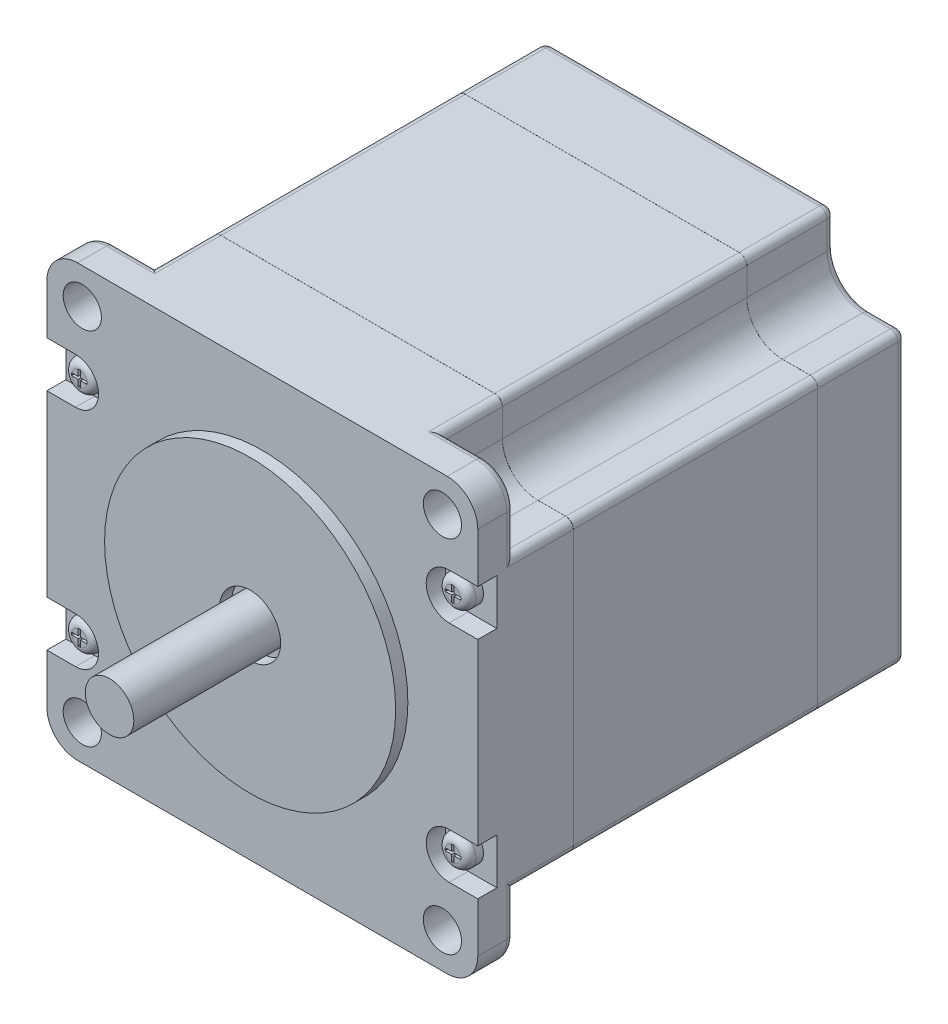
SolidWorks part; units mm, degrees
material "1060 Alloy"
ref_plane "Front Plane" through (0, 0, 0) normal (0, 0, 1) x (1, 0, 0)
ref_plane "Top Plane" through (0, 0, 0) normal (0, 1, 0) x (1, 0, 0)
ref_plane "Right Plane" through (0, 0, 0) normal (1, 0, 0) x (0, 0, -1)
sketch "Sketch1" plane through (0, 0, 0) normal (0, 0, 1) x (1, 0, 0)
  line L1 (-28.2, -28.2) -> (28.2, -28.2)
  line L2 (-28.2, -28.2) -> (-28.2, 28.2)
  line L3 (-28.2, 28.2) -> (28.2, 28.2)
  line L4 (28.2, -28.2) -> (28.2, 28.2)
  line L5 (-28.2, -28.2) -> (28.2, 28.2) construction
  line L6 (-28.2, 28.2) -> (28.2, -28.2) construction
  point P0 (0, 0)
  dimension "D1" = 56.4
  dimension "D2" = 56.4
extrude "Boss-Extrude1" add sketch "Sketch1" against normal blind 56
sketch "Sketch2" plane through (0, 0, 0) normal (0, 0, 1) x (1, 0, 0)
  circle A0 centre (0, 0) radius 19.05
  dimension "D1" = 38.1
extrude "Boss-Extrude2" add sketch "Sketch2" along normal blind 1.6
sketch "Sketch3" plane through (0, 0, 0) normal (0, 0, 1) x (1, 0, 0)
  line L0 (-23.57, 23.57) -> (23.57, 23.57) construction
  line L1 (23.57, 23.57) -> (23.57, -23.57) construction
  line L2 (23.57, -23.57) -> (-23.57, -23.57) construction
  line L3 (-23.57, -23.57) -> (-23.57, 23.57) construction
  line L4 (23.57, 23.57) -> (-23.57, -23.57) construction
  circle A0 centre (-23.57, 23.57) radius 2.5
  circle A1 centre (23.57, 23.57) radius 2.5
  circle A2 centre (23.57, -23.57) radius 2.5
  circle A3 centre (-23.57, -23.57) radius 2.5
  dimension "D1" = 5
  dimension "D2" = 47.14
  dimension "D3" = 47.14
extrude "Cut-Extrude1" cut sketch "Sketch3" against normal blind 10
sketch "Sketch6" plane through (0, 0, -56) normal (0, 0, -1) x (-1, 0, 0)
  line L0 (-18.92, 23.57) -> (-18.92, 28.2)
  line L1 (-28.2, 28.2) -> (28.2, 28.2) construction
  line L2 (-23.57, 18.92) -> (-28.2, 18.92)
  line L3 (-28.2, -28.2) -> (-28.2, 28.2) construction
  line L4 (-28.2, 0) -> (28.2, 0) construction
  line L5 (28.2, 28.2) -> (28.2, -28.2) construction
  line L6 (0, 28.2) -> (0, -28.2) construction
  line L7 (28.2, -28.2) -> (-28.2, -28.2) construction
  line L8 (-18.92, 28.2) -> (-28.2, 28.2)
  line L9 (-28.2, 28.2) -> (-28.2, 18.92)
  line L10 (28.2, 28.2) -> (28.2, 18.92)
  line L11 (18.92, 28.2) -> (28.2, 28.2)
  line L12 (23.57, 18.92) -> (28.2, 18.92)
  line L13 (18.92, 23.57) -> (18.92, 28.2)
  line L14 (-28.2, -28.2) -> (-28.2, -18.92)
  line L15 (-18.92, -28.2) -> (-28.2, -28.2)
  line L16 (-23.57, -18.92) -> (-28.2, -18.92)
  line L17 (-18.92, -23.57) -> (-18.92, -28.2)
  line L18 (18.92, -23.57) -> (18.92, -28.2)
  line L19 (23.57, -18.92) -> (28.2, -18.92)
  line L20 (18.92, -28.2) -> (28.2, -28.2)
  line L21 (28.2, -28.2) -> (28.2, -18.92)
  circle A0 centre (-23.57, 23.57) radius 2.5 construction
  arc A4 (23.57, 18.92) -> (18.92, 23.57) centre (23.57, 23.57) cw
  arc A5 (-23.57, -18.92) -> (-18.92, -23.57) centre (-23.57, -23.57) cw
  arc A6 (-23.57, 18.92) -> (-18.92, 23.57) centre (-23.57, 23.57) ccw
  arc A7 (23.57, -18.92) -> (18.92, -23.57) centre (23.57, -23.57) ccw
  dimension "D1" = 4.65
extrude "Cut-Extrude2" cut sketch "Sketch6" against normal offset from surface (51.2 mm away) 4.8 up to face at (-21.07, -23.57, 0)
fillet "Fillet1" radius 4 4 edges at (28.2, -28.2, -2.4) (-28.2, -28.2, -2.4) (-28.2, 28.2, -2.4) (28.2, 28.2, -2.4)
sketch "Sketch7" plane through (-28.2, 0, 0) normal (-1, 0, 0) x (0, 0, 1)
  line L0 (-4.8, 28.2) -> (-56, 28.2) construction
  line L1 (-12.51, -28.2) -> (-44.49, -28.2)
  line L2 (-12.51, -28.2) -> (-12.51, 28.2)
  line L3 (-12.51, 28.2) -> (-44.49, 28.2)
  line L4 (-44.49, -28.2) -> (-44.49, 28.2)
  line L5 (-12.51, -28.2) -> (-44.49, 28.2) construction
  line L6 (-12.51, 28.2) -> (-44.49, -28.2) construction
  line L7 (-28.5, -28.2) -> (-28.5, 28.2) construction
  line L9 (-56, 0) -> (0, 0) construction
  line L10 (-56, 18.92) -> (-56, -18.92) construction
  line L11 (-44.5, -28.21) -> (-44.5, 28.21)
  line L12 (-12.5, 28.21) -> (-44.5, 28.21)
  line L13 (-12.5, -28.21) -> (-12.5, 28.21)
  line L14 (-12.5, -28.21) -> (-44.5, -28.21)
  point P0 (-28.5, 0)
  dimension "D1" = 32
  dimension "D3" = 11.5
  dimension "D2" = 0.01
extrude "Cut-Extrude3" cut sketch "Sketch7" against normal through all
sketch "Sketch8" plane through (0, 0, -56) normal (0, 0, -1) x (-1, 0, 0)
  circle A0 centre (0, 0) radius 6
  dimension "D1" = 12
extrude "Cut-Extrude4" cut sketch "Sketch8" against normal blind 3
sketch "Sketch9" plane through (0, 0, -53) normal (0, 0, -1) x (-1, 0, 0)
  circle A0 centre (0, 0) radius 3.175
  dimension "D1" = 6.35
extrude "Boss-Extrude3" add sketch "Sketch9" along normal blind 1.5 separate body
chamfer "Chamfer1" distance 0.5 angle 45 1 edges at (-3.175, 0, -54.5)
sketch "Sketch10" plane through (0, 0, 1.6) normal (0, 0, 1) x (1, 0, 0)
  circle A0 centre (0, 0) radius 4
  dimension "D1" = 8
extrude "Cut-Extrude5" cut sketch "Sketch10" against normal up to surface (1.6 mm away) up to face at (-21.07, -23.57, 0)
sketch "Sketch11" plane through (0, 0, 0) normal (0, 0, 1) x (1, 0, 0)
  circle A0 centre (0, 0) radius 3.175
  dimension "D1" = 6.35
extrude "Boss-Extrude4" add sketch "Sketch11" along normal blind 20 separate body
sketch "Sketch13" plane through (0, 0, 0) normal (0, 0, 1) x (1, 0, 0)
  line L0 (-28.2, 24.2) -> (-28.2, -24.2) construction
  line L1 (24.2, 28.2) -> (-24.2, 28.2) construction
  line L2 (-24.45, 17.7) -> (-28.2, 17.7)
  line L3 (-28.2, 17.7) -> (-28.2, 11.7)
  line L4 (-28.2, 11.7) -> (-24.45, 11.7)
  line L5 (0, 28.2) -> (0, 0) construction
  line L6 (-28.2, 0) -> (0, 0) construction
  line L7 (28.2, 11.7) -> (24.45, 11.7)
  line L8 (28.2, 17.7) -> (28.2, 11.7)
  line L9 (24.45, 17.7) -> (28.2, 17.7)
  line L10 (24.45, -17.7) -> (28.2, -17.7)
  line L11 (28.2, -17.7) -> (28.2, -11.7)
  line L12 (28.2, -11.7) -> (24.45, -11.7)
  line L13 (-28.2, -11.7) -> (-24.45, -11.7)
  line L14 (-28.2, -17.7) -> (-28.2, -11.7)
  line L15 (-24.45, -17.7) -> (-28.2, -17.7)
  arc A0 (-24.45, 11.7) -> (-24.45, 17.7) centre (-24.45, 14.7) ccw
  arc A1 (24.45, 11.7) -> (24.45, 17.7) centre (24.45, 14.7) cw
  arc A2 (24.45, -11.7) -> (24.45, -17.7) centre (24.45, -14.7) ccw
  arc A3 (-24.45, -11.7) -> (-24.45, -17.7) centre (-24.45, -14.7) cw
  dimension "D1" = 6
  dimension "D2" = 3.75
  dimension "D3" = 13.5
extrude "Cut-Extrude7" cut sketch "Sketch13" against normal blind 2.5
sketch "Sketch14" plane through (0, 0, -2.5) normal (0, 0, 1) x (1, 0, 0)
  circle A0 centre (-24.45, 14.7) radius 2
  circle A1 centre (24.45, 14.7) radius 2
  circle A2 centre (24.45, -14.7) radius 2
  circle A3 centre (-24.45, -14.7) radius 2
  dimension "D1" = 4
extrude "Boss-Extrude5" add sketch "Sketch14" along normal blind 2 separate body
fillet "Fillet2" radius 1 1 edges at (-22.45, 14.7, -0.5)
fillet "Fillet3" radius 1 1 edges at (-22.45, -14.7, -0.5)
fillet "Fillet4" radius 1 1 edges at (26.45, -14.7, -0.5)
fillet "Fillet5" radius 1 1 edges at (26.45, 14.7, -0.5)
sketch "Sketch15" plane through (0, 0, -0.5) normal (0, 0, 1) x (1, 0, 0)
  line L0 (-24.6123, 14.8623) -> (-24.6123, 15.7182)
  line L1 (-24.6123, 13.6818) -> (-24.2877, 13.6818)
  line L2 (-24.6123, 13.6818) -> (-24.6123, 14.5377)
  line L3 (-24.6123, 15.7182) -> (-24.2877, 15.7182)
  line L4 (-24.2877, 13.6818) -> (-24.2877, 14.5377)
  line L5 (-24.6123, 13.6818) -> (-24.2877, 15.7182) construction
  line L6 (-24.6123, 15.7182) -> (-24.2877, 13.6818) construction
  line L7 (-25.4732, 14.5377) -> (-24.6123, 14.5377)
  line L8 (-25.4732, 14.5377) -> (-25.4732, 14.8623)
  line L9 (-25.4732, 14.8623) -> (-24.6123, 14.8623)
  line L10 (-23.4268, 14.5377) -> (-23.4268, 14.8623)
  line L11 (-25.4732, 14.5377) -> (-23.4268, 14.8623) construction
  line L12 (-25.4732, 14.8623) -> (-23.4268, 14.5377) construction
  line L13 (-24.2877, 14.5377) -> (-23.4268, 14.5377)
  line L14 (-24.2877, 14.8623) -> (-23.4268, 14.8623)
  line L15 (-24.2877, 14.8623) -> (-24.2877, 15.7182)
  line L16 (0, 28.2) -> (0, 21.2733) construction
  line L17 (24.2, 28.2) -> (-24.2, 28.2) construction
  line L18 (-28.2, 0) -> (-21.4297, 0) construction
  line L19 (-28.2, 11.7) -> (-28.2, -11.7) construction
  line L20 (25.4732, 14.8623) -> (23.4268, 14.5377) construction
  line L21 (25.4732, 14.5377) -> (23.4268, 14.8623) construction
  line L22 (24.6123, 15.7182) -> (24.2877, 13.6818) construction
  line L23 (24.6123, 13.6818) -> (24.2877, 15.7182) construction
  line L24 (24.2877, 14.8623) -> (24.2877, 15.7182)
  line L25 (24.2877, 14.8623) -> (23.4268, 14.8623)
  line L26 (24.2877, 14.5377) -> (23.4268, 14.5377)
  line L27 (23.4268, 14.5377) -> (23.4268, 14.8623)
  line L28 (25.4732, 14.8623) -> (24.6123, 14.8623)
  line L29 (25.4732, 14.5377) -> (25.4732, 14.8623)
  line L30 (25.4732, 14.5377) -> (24.6123, 14.5377)
  line L31 (24.2877, 13.6818) -> (24.2877, 14.5377)
  line L32 (24.6123, 15.7182) -> (24.2877, 15.7182)
  line L33 (24.6123, 13.6818) -> (24.6123, 14.5377)
  line L34 (24.6123, 13.6818) -> (24.2877, 13.6818)
  line L35 (24.6123, 14.8623) -> (24.6123, 15.7182)
  line L36 (24.6123, -13.6818) -> (24.2877, -15.7182) construction
  line L37 (24.6123, -15.7182) -> (24.2877, -13.6818) construction
  line L38 (25.4732, -14.5377) -> (23.4268, -14.8623) construction
  line L39 (25.4732, -14.8623) -> (23.4268, -14.5377) construction
  line L40 (24.6123, -14.8623) -> (24.6123, -15.7182)
  line L41 (24.6123, -13.6818) -> (24.2877, -13.6818)
  line L42 (24.6123, -13.6818) -> (24.6123, -14.5377)
  line L43 (24.6123, -15.7182) -> (24.2877, -15.7182)
  line L44 (24.2877, -13.6818) -> (24.2877, -14.5377)
  line L45 (25.4732, -14.5377) -> (24.6123, -14.5377)
  line L46 (25.4732, -14.5377) -> (25.4732, -14.8623)
  line L47 (25.4732, -14.8623) -> (24.6123, -14.8623)
  line L48 (23.4268, -14.5377) -> (23.4268, -14.8623)
  line L49 (24.2877, -14.5377) -> (23.4268, -14.5377)
  line L50 (24.2877, -14.8623) -> (23.4268, -14.8623)
  line L51 (24.2877, -14.8623) -> (24.2877, -15.7182)
  line L52 (-25.4732, -14.8623) -> (-23.4268, -14.5377) construction
  line L53 (-25.4732, -14.5377) -> (-23.4268, -14.8623) construction
  line L54 (-24.6123, -15.7182) -> (-24.2877, -13.6818) construction
  line L55 (-24.6123, -13.6818) -> (-24.2877, -15.7182) construction
  line L56 (-24.2877, -14.8623) -> (-24.2877, -15.7182)
  line L57 (-24.2877, -14.8623) -> (-23.4268, -14.8623)
  line L58 (-24.2877, -14.5377) -> (-23.4268, -14.5377)
  line L59 (-23.4268, -14.5377) -> (-23.4268, -14.8623)
  line L60 (-25.4732, -14.8623) -> (-24.6123, -14.8623)
  line L61 (-25.4732, -14.5377) -> (-25.4732, -14.8623)
  line L62 (-25.4732, -14.5377) -> (-24.6123, -14.5377)
  line L63 (-24.2877, -13.6818) -> (-24.2877, -14.5377)
  line L64 (-24.6123, -15.7182) -> (-24.2877, -15.7182)
  line L65 (-24.6123, -13.6818) -> (-24.6123, -14.5377)
  line L66 (-24.6123, -13.6818) -> (-24.2877, -13.6818)
  line L67 (-24.6123, -14.8623) -> (-24.6123, -15.7182)
  point P0 (-24.45, 14.7)
  point P6 (-24.45, 14.7)
  point P36 (24.45, 14.7)
  point P49 (24.45, -14.7)
  point P62 (-24.45, -14.7)
extrude "Cut-Extrude8" cut sketch "Sketch15" against normal blind 1.2
chamfer "Chamfer2" distance 1 angle 45 4 edges at (-24.45, 13.6818, -1.7) (-23.4268, 14.7, -1.7) (-25.4732, 14.7, -1.7) (-24.45, 15.7182, -1.7)
chamfer "Chamfer3" distance 1 angle 45 4 edges at (25.4732, 14.7, -1.7) (24.45, 15.7182, -1.7) (24.45, 13.6818, -1.7) (23.4268, 14.7, -1.7)
chamfer "Chamfer4" distance 1 angle 45 4 edges at (24.45, -13.6818, -1.7) (24.45, -15.7182, -1.7) (23.4268, -14.7, -1.7) (25.4732, -14.7, -1.7)
chamfer "Chamfer5" distance 1 angle 45 4 edges at (-23.4268, -14.7, -1.7) (-25.4732, -14.7, -1.7) (-24.45, -15.7182, -1.7) (-24.45, -13.6818, -1.7)
fillet "Fillet6" radius 1 25 edges at (-20.282, -20.282, -56) (-18.92, -25.885, -56) (0, -28.2, -56) (18.92, -25.885, -56) (20.282, -20.282, -56) (25.885, -18.92, -56) (28.2, 0, -56) (25.885, 18.92, -56) (20.282, 20.282, -56) (18.92, 25.885, -56) (0, 28.2, -56) (-18.92, 25.885, -56) (-20.282, 20.282, -56) (-25.885, 18.92, -56) (-28.2, 0, -56) (-25.885, -18.92, -56) (-6, 0, -56) (-18.92, 28.2, -50.25) (-28.2, 18.92, -50.25) (-28.2, -18.92, -50.25) (-18.92, -28.2, -50.25) (18.92, -28.2, -50.25) (28.2, -18.92, -50.25) (28.2, 18.92, -50.25) (18.92, 28.2, -50.25)
fillet "Fillet7" radius 1 8 edges at (-28.2, 18.92, -28.5) (-28.2, -18.92, -28.5) (-18.92, -28.2, -28.5) (18.92, -28.2, -28.5) (28.2, -18.92, -28.5) (28.2, 18.92, -28.5) (18.92, 28.2, -28.5) (-18.92, 28.2, -28.5)
fillet "Fillet8" radius 1 20 edges at (-21.56, -28.2, -4.8) (-28.2, -21.56, -4.8) (28.2, -21.56, -4.8) (21.56, -28.2, -4.8) (21.56, 28.2, -4.8) (28.2, 21.56, -4.8) (-28.2, 21.56, -4.8) (-21.56, 28.2, -4.8) (-28.2, -18.92, -8.65) (-27.0284, -27.0284, -4.8) (-18.92, -28.2, -8.65) (18.92, -28.2, -8.65) (27.0284, -27.0284, -4.8) (28.2, -18.92, -8.65) (28.2, 18.92, -8.65) (27.0284, 27.0284, -4.8) (18.92, 28.2, -8.65) (-28.2, 18.92, -8.65) (-18.92, 28.2, -8.65) (-27.0284, 27.0284, -4.8)
